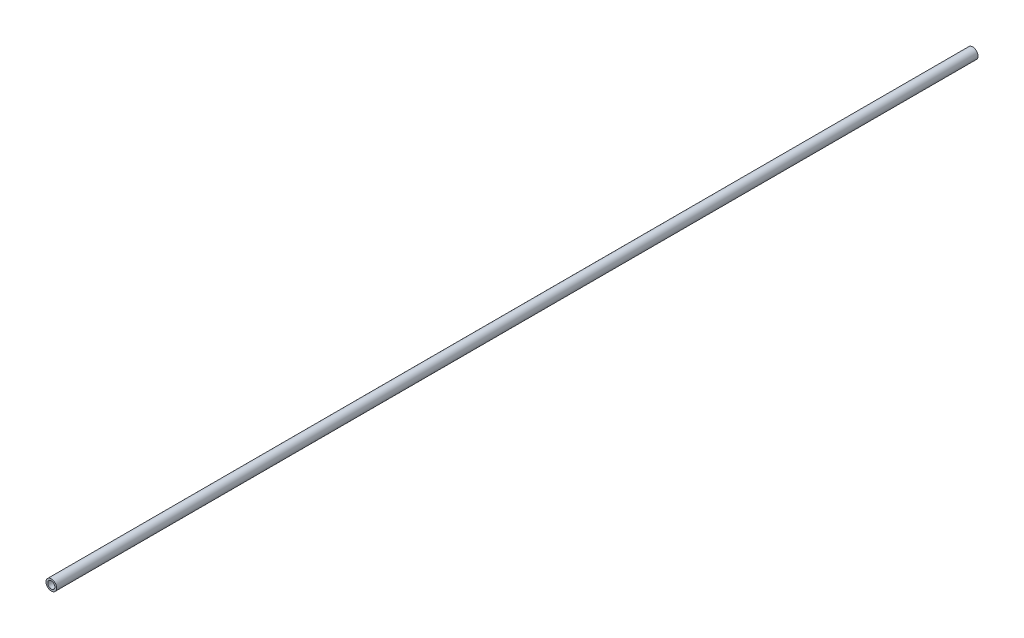
SolidWorks part; units mm, degrees
ref_plane "Front Plane" through (0, 0, 0) normal (0, 0, 1) x (1, 0, 0)
ref_plane "Top Plane" through (0, 0, 0) normal (0, 1, 0) x (1, 0, 0)
ref_plane "Right Plane" through (0, 0, 0) normal (1, 0, 0) x (0, 0, -1)
sketch "Sketch1" plane through (0, 0, 0) normal (0, 0, 1) x (1, 0, 0)
  circle A0 centre (-116.373, -116.373) radius 3.175
  circle A1 centre (-116.373, -116.373) radius 4.7625
  point P4 (0, 0)
  point P5 (-116.373, -116.373)
  dimension "D1" = 9.525
  dimension "D2" = 6.35
extrude "Boss-Extrude1" add sketch "Sketch1" along normal blind 825.5
